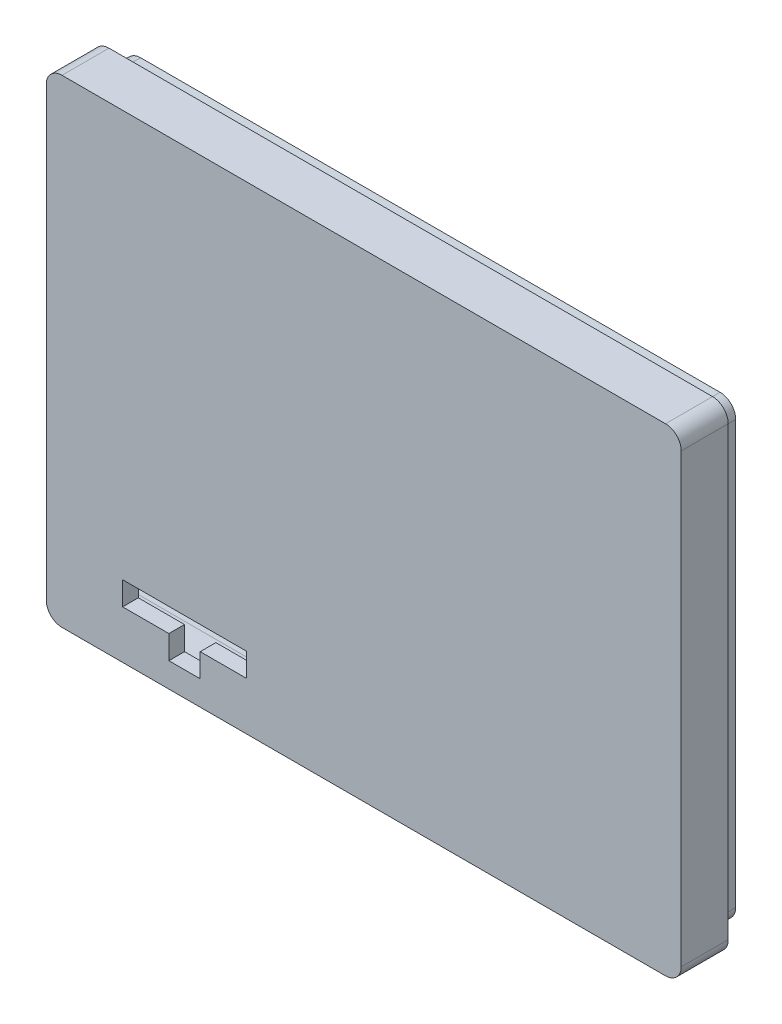
SolidWorks part; units mm, degrees
ref_plane "Front" through (0, 0, 0) normal (0, 0, 1) x (1, 0, 0)
ref_plane "Top" through (0, 0, 0) normal (0, 1, 0) x (1, 0, 0)
ref_plane "Right" through (0, 0, 0) normal (1, 0, 0) x (0, 0, -1)
sketch "Esquisse1" plane through (0, 0, 0) normal (0, 0, 1) x (1, 0, 0)
  line L1 (0, 0) -> (81, 0)
  line L2 (0, 0) -> (0, 61)
  line L3 (0, 61) -> (81, 61)
  line L4 (81, 0) -> (81, 61)
  dimension "D1" = 81
  dimension "D2" = 61
extrude "Extru.-Mince1" add sketch "Esquisse1" along normal blind 6 thin thin type one direction reverse wall 2.5
sketch "Esquisse2" plane through (0, 0, 0) normal (0, 0, 1) x (1, 0, 0)
  line L0 (2.5, 58.5) -> (2.5, 2.5)
  line L1 (2.5, 2.5) -> (78.5, 2.5)
  line L2 (78.5, 2.5) -> (78.5, 58.5)
  line L3 (78.5, 58.5) -> (2.5, 58.5)
  line L4 (78.5, 2.5) -> (78.5, 58.5) construction
  line L5 (2.5, 58.5) -> (2.5, 2.5) construction
  line L6 (78.5, 58.5) -> (2.5, 58.5) construction
  dimension "D2" = 56
  dimension "D3" = 56
extrude "Extru.-Mince2" add sketch "Esquisse2" along normal blind 6 and the other way blind 2.5 draft 1 thin thin type one direction wall 1
ref_plane "Plan1" through (0, 0, 6) normal (0, 0, 1) x (1, 0, 0)
sketch "Esquisse3" plane through (0, 0, 6) normal (0, 0, 1) x (1, 0, 0)
  line L1 (2.5, 58.5) -> (78.5, 58.5)
  line L2 (2.5, 58.5) -> (2.5, 2.5)
  line L3 (2.5, 2.5) -> (78.5, 2.5)
  line L4 (78.5, 58.5) -> (78.5, 2.5)
  line L7 (2.5, 2.5) -> (78.5, 2.5) construction
  line L11 (2.5, 58.5) -> (2.5, 2.5) construction
  line L12 (78.5, 2.5) -> (78.5, 58.5) construction
  line L13 (78.5, 58.5) -> (2.5, 58.5) construction
extrude "Boss.-Extru.1" add sketch "Esquisse3" against normal blind 2
fillet "Congé1" radius 2 4 edges at (1.5218, 59.4782, -1.25) (1.5218, 1.5218, -1.25) (79.4782, 1.5218, -1.25) (79.4782, 59.4782, -1.25)
fillet "Congé2" radius 2 4 edges at (81, 61, 3) (81, 0, 3) (0, 0, 3) (0, 61, 3)
sketch "Esquisse4" plane through (0, 0, 0) normal (1, 0, 0) x (0, 0, -1)
  line L0 (0, 59) -> (0, 2) construction
  line L2 (6.75, 50.8) -> (-3.25, 50.8)
  line L3 (6.75, 50.8) -> (6.75, 44.3)
  line L4 (6.75, 44.3) -> (-3.25, 44.3)
  line L5 (-3.25, 50.8) -> (-3.25, 44.3)
  line L6 (0, 61) -> (-6, 61) construction
  dimension "D1" = 6.5
  dimension "D2" = 10
  dimension "D3" = 10.2
  dimension "D4" = 3.25
extrude "Enlèv. mat.-Extru.1" cut sketch "Esquisse4" along normal blind 12
ref_plane "Plan2" through (2.4992, 0, -0.0436) normal (0.9998, 0, -0.0175) x (-0.0175, 0, -0.9998)
sketch "Esquisse5" plane through (2.4992, 0, -0.0436) normal (0.9998, 0, -0.0175) x (-0.0175, 0, -0.9998)
  line L4 (-0.0436, 32.0521) -> (-0.0436, 63.0479) construction
  line L5 (-0.0349, 61) -> (-6.034, 61) construction
  line L7 (-0.0436, 52.05) -> (9.1156, 52.05)
  line L8 (9.1156, 52.05) -> (9.1156, 43.05)
  line L9 (9.1156, 43.05) -> (-0.0436, 43.05)
  line L10 (-0.0436, 44.3) -> (-0.0436, 2.5) construction
  arc A0 (-0.0436, 43.05) -> (-0.0436, 52.05) centre (-0.0436, 47.55) cw
  dimension "D1" = 4.5
  dimension "D2" = 13.45
extrude "Enlèv. mat.-Extru.2" cut sketch "Esquisse5" against normal blind 1.5
sketch "Esquisse6" plane through (0, 0, 0) normal (0, 0, 1) x (1, 0, 0)
  line L0 (40.5, 89.7306) -> (40.5, -23.1003) construction
  line L1 (81, 2) -> (81, 59) construction
  line L2 (0, 59) -> (0, 2) construction
  line L3 (17.64, 8.5645) -> (17.64, 35.3003) construction
  line L4 (25.54, 9.14) -> (9.74, 9.14)
  line L5 (25.54, 9.14) -> (25.54, 6.14)
  line L6 (25.54, 6.14) -> (19.64, 6.14)
  line L7 (9.74, 9.14) -> (9.74, 6.14)
  line L8 (15.64, 6.14) -> (9.74, 6.14)
  line L10 (15.64, 6.14) -> (15.64, 3.14)
  line L11 (15.64, 3.14) -> (19.64, 3.14)
  line L12 (19.64, 6.14) -> (19.64, 3.14)
  line L13 (93.1241, 30.5) -> (-32.1819, 30.5) construction
  line L14 (7.1793, 7.64) -> (40.5, 7.64) construction
  line L15 (2.5, 2.5) -> (78.5, 2.5) construction
  line L16 (78.5, 58.5) -> (2.5, 58.5) construction
  dimension "D1" = 22.86
  dimension "D2" = 3
  dimension "D3" = 15.8
  dimension "D4" = 4
  dimension "D5" = 3
  dimension "D6" = 22.86
extrude "Enlèv. mat.-Extru.3" cut sketch "Esquisse6" along normal blind 11.5
